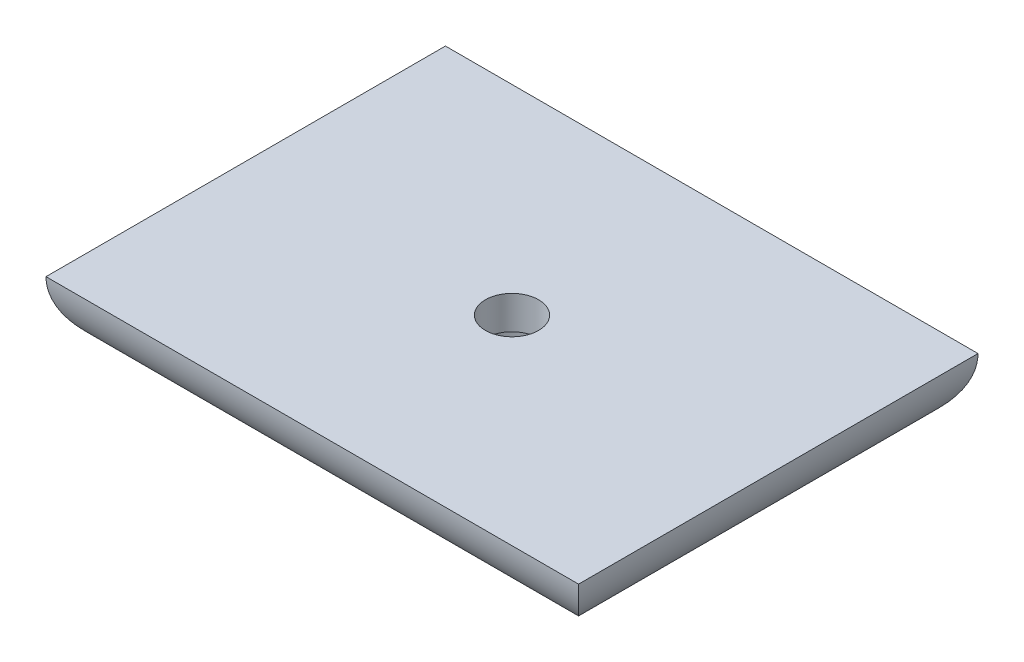
SolidWorks part; units mm, degrees
ref_plane "Plan de face" through (0, 0, 0) normal (0, 0, 1) x (1, 0, 0)
ref_plane "Plan de dessus" through (0, 0, 0) normal (0, 1, 0) x (1, 0, 0)
ref_plane "Plan de droite" through (0, 0, 0) normal (1, 0, 0) x (0, 0, -1)
sketch "Esquisse1" plane through (0, 0, 0) normal (0, 1, 0) x (1, 0, 0)
  line L1 (20, 15) -> (-20, 15)
  line L2 (20, 15) -> (20, -15)
  line L3 (20, -15) -> (-20, -15)
  line L4 (-20, 15) -> (-20, -15)
  line L5 (20, 15) -> (-20, -15) construction
  line L6 (20, -15) -> (-20, 15) construction
  circle A0 centre (0, 0) radius 2
  point P0 (0, 0)
  dimension "D3" = 4
  dimension "D1" = 30
  dimension "D2" = 40
extrude "BASE" add sketch "Esquisse1" along normal blind 5
fillet "EXT" radius 5 4 edges at (-20, 0, 0) (0, 0, -15) (20, 0, 0) (0, 0, 15)
sketch "Esquisse2" plane through (0, 0, 0) normal (0, -1, 0) x (-1, 0, 0)
  circle A0 centre (0, 0) radius 4
  dimension "D1" = 8
extrude "ACCES VIS" cut sketch "Esquisse2" against normal blind 2.5
